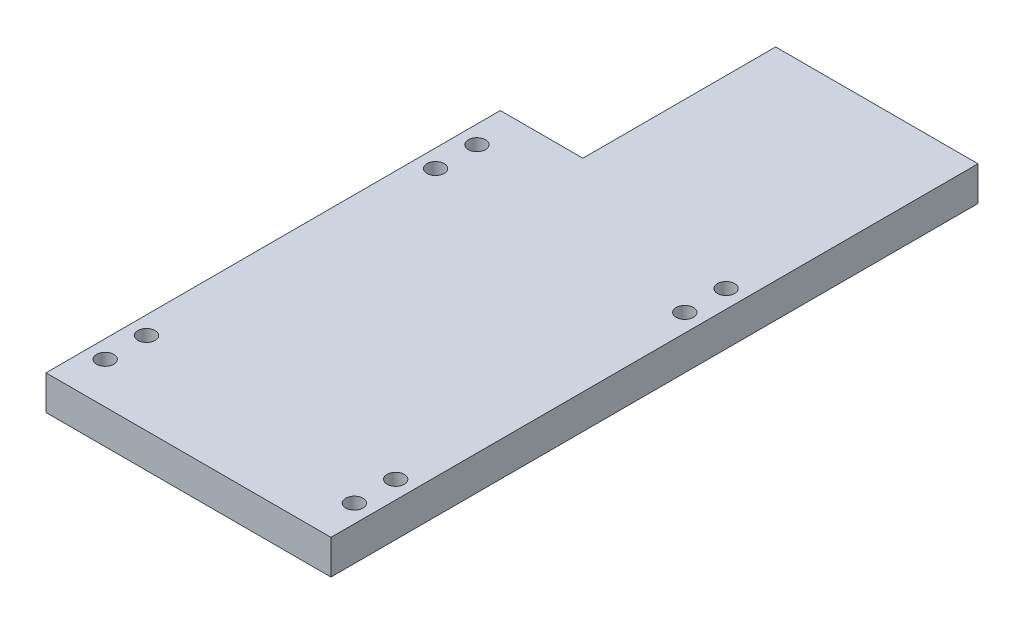
SolidWorks part; units mm, degrees
ref_plane "Front Plane" through (0, 0, 0) normal (0, 0, 1) x (1, 0, 0)
ref_plane "Top Plane" through (0, 0, 0) normal (0, 1, 0) x (1, 0, 0)
ref_plane "Right Plane" through (0, 0, 0) normal (1, 0, 0) x (0, 0, -1)
sketch "Sketch1" plane through (0, 0, 0) normal (0, 1, 0) x (1, 0, 0)
  line L1 (0, 0) -> (-53.594, 0)
  line L2 (0, 0) -> (0, 76.2)
  line L3 (0, 76.2) -> (-53.594, 76.2)
  line L4 (-53.594, 0) -> (-53.594, 76.2)
  dimension "D1" = 76.2
  dimension "D2" = 53.594
extrude "Boss-Extrude1" add sketch "Sketch1" along normal blind 6.35
sketch "Sketch2" plane through (0, 6.35, 0) normal (0, 1, 0) x (1, 0, 0)
  line L0 (0, 0) -> (0, 76.2) construction
  line L1 (-53.594, 0) -> (0, 0) construction
  circle A0 centre (-3.81, 7.62) radius 1.5875
  circle A4 centre (-3.81, 68.58) radius 1.5875
  dimension "D2" = 3.175
  dimension "D1" = 3.81
  dimension "D3" = 7.62
  dimension "D4" = 68.58
extrude "Hole Cuts 1" cut sketch "Sketch2" against normal through all
sketch "Sketch6" plane through (0, 0, 0) normal (0, 0, 1) x (1, 0, 0)
  line L1 (0, 6.35) -> (-53.594, 6.35)
  line L2 (0, 6.35) -> (0, 0)
  line L3 (0, 0) -> (-53.594, 0)
  line L4 (-53.594, 6.35) -> (-53.594, 0)
extrude "Boss-Extrude3" add sketch "Sketch6" along normal blind 7.62
ref_plane "KORAL!!!" through (-26.797, 0, 0) normal (1, 0, 0) x (0, 0, -1)
sketch "Sketch7" plane through (0, 6.35, 0) normal (0, 1, 0) x (1, 0, 0)
  line L0 (0, -7.62) -> (0, 76.2) construction
  line L1 (0, -7.62) -> (-53.594, -7.62) construction
  circle A0 centre (-3.81, 0) radius 1.5875
  circle A1 centre (-3.81, 7.62) radius 1.5875 construction
  circle A2 centre (-3.81, 60.96) radius 1.5875
  dimension "D1" = 3.81
  dimension "D2" = 7.62
  dimension "D3" = 68.58
extrude "Hole Cuts 2" cut sketch "Sketch7" against normal up to next
sketch "Sketch3" plane through (0, 6.35, 0) normal (0, 1, 0) x (1, 0, 0)
  line L1 (0, 76.2) -> (0, -7.62)
  line L2 (-0.508, -7.62) -> (-0.508, 76.2)
  line L3 (0, 76.2) -> (-53.594, 76.2) construction
  line L4 (-0.508, 76.2) -> (0, 76.2)
  line L6 (0, -7.62) -> (-53.594, -7.62) construction
  line L7 (0, -7.62) -> (-0.508, -7.62)
  dimension "D1" = 0.508
extrude "Cut-Extrude2" cut sketch "Sketch3" against normal up to next
mirror "Mirror1" about plane through (-26.797, 0, 0) normal (1, 0, 0) of "Cut-Extrude2", "Hole Cuts 2", "Hole Cuts 1"
sketch "Sketch8" plane through (0, 0, -76.2) normal (0, 0, -1) x (-1, 0, 0)
  line L0 (0.508, 0) -> (53.086, 0) construction
  line L1 (0.508, 6.35) -> (37.846, 6.35)
  line L2 (0.508, 6.35) -> (0.508, 0)
  line L3 (0.508, 0) -> (37.846, 0)
  line L4 (37.846, 6.35) -> (37.846, 0)
  line L5 (53.086, 0) -> (53.086, 6.35) construction
  dimension "D1" = 15.24
extrude "Boss-Extrude4" add sketch "Sketch8" along normal blind 35.56
